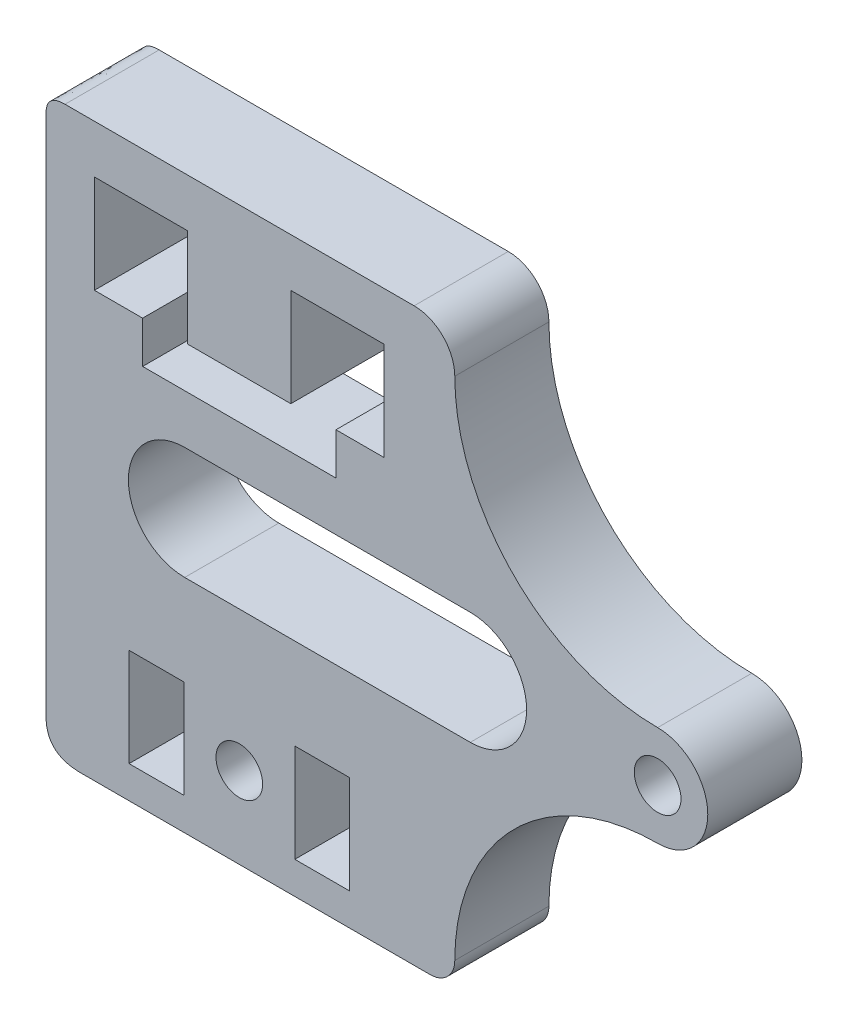
SolidWorks part; units mm, degrees
material "Acrylic (Medium-high impact)"
ref_plane "Front Plane" through (0, 0, 0) normal (0, 0, 1) x (1, 0, 0)
ref_plane "Top Plane" through (0, 0, 0) normal (0, 1, 0) x (1, 0, 0)
ref_plane "Right Plane" through (0, 0, 0) normal (1, 0, 0) x (0, 0, -1)
sketch "Sketch1" plane through (0, 0, 0) normal (0, 0, 1) x (1, 0, 0)
  line L0 (405.5669, 551.1889) -> (405.5669, 553.7889)
  line L1 (396.3551, 553.7889) -> (402.763, 553.7889)
  line L2 (393.5512, 553.7889) -> (393.5512, 551.1889)
  line L3 (393.5512, 551.1889) -> (405.5669, 551.1889)
  line L4 (390.5551, 559.8889) -> (390.5551, 553.7889)
  line L5 (393.5512, 553.7889) -> (390.5551, 553.7889)
  line L6 (396.3551, 559.8889) -> (390.5551, 559.8889)
  line L7 (396.3551, 553.7889) -> (396.3551, 559.8889)
  line L8 (405.5669, 553.7889) -> (408.563, 553.7889)
  line L9 (408.563, 553.7889) -> (408.563, 559.8889)
  line L10 (402.763, 559.8889) -> (402.763, 553.7889)
  line L11 (408.563, 559.8889) -> (402.763, 559.8889)
  line L12 (392.709, 535.4889) -> (392.709, 529.3889)
  line L13 (392.709, 529.3889) -> (396.109, 529.3889)
  line L14 (396.109, 535.4889) -> (392.709, 535.4889)
  line L15 (396.109, 529.3889) -> (396.109, 535.4889)
  line L16 (403.009, 529.3889) -> (406.4091, 529.3889)
  line L17 (406.4091, 529.3889) -> (406.4091, 535.4889)
  line L18 (403.009, 535.4889) -> (403.009, 529.3889)
  line L19 (406.4091, 535.4889) -> (403.009, 535.4889)
  line L20 (388.7281, 562.8889) -> (410.4246, 562.8889)
  line L21 (387.5551, 561.7172) -> (387.5551, 529.5596)
  line L22 (389.7281, 527.3889) -> (411.4246, 527.3889)
  line L23 (-605.591, 535.4889) -> (49394.409, 535.4889) construction
  line L24 (396.1657, 548.1389) -> (413.9157, 548.1389)
  line L25 (396.1657, 541.1389) -> (413.9157, 541.1389)
  line L26 (-600.441, 544.6389) -> (49399.559, 544.6389) construction
  line L27 (398.109, 532.4389) -> (396.109, 532.4389) construction
  line L28 (401.009, 532.4389) -> (403.009, 532.4389) construction
  line L29 (399.559, -466.6171) -> (399.559, 49533.3829) construction
  line L30 (425.559, -455.7473) -> (425.559, 49544.2527) construction
  line L31 (-608.8734, 553.7889) -> (49391.1266, 553.7889) construction
  line L32 (421.909, 544.6389) -> (421.909, 535.4889) construction
  line L33 (421.909, 544.6389) -> (421.909, 553.7889) construction
  line L34 (412.9514, 560.3621) -> (412.9514, 528.9157) construction
  circle A0 centre (425.559, 544.6389) radius 1.45
  arc A1 (396.1657, 548.1389) -> (396.1657, 541.1389) centre (396.1657, 544.6389) ccw
  circle A2 centre (399.559, 532.4389) radius 1.45
  arc A3 (412.9514, 528.9157) -> (425.559, 541.5233) centre (425.559, 528.9157) cw
  arc A4 (412.9514, 560.3621) -> (425.559, 547.7545) centre (425.559, 560.3621) ccw
  arc A5 (425.559, 547.7545) -> (425.559, 541.5233) centre (425.559, 544.6389) cw
  arc A7 (413.9157, 548.1389) -> (413.9157, 541.1389) centre (413.9157, 544.6389) cw
  arc A8 (411.4246, 527.3889) -> (412.9514, 528.9157) centre (411.4246, 528.9157) ccw
  arc A9 (410.4246, 562.8889) -> (412.9514, 560.3621) centre (410.4246, 560.3621) cw
  spline S36 degree 2 poles (387.5551, 561.7172) (387.4906, 562.8889) (388.7281, 562.8889) knots 0 0 0 1 1 1
  spline S37 degree 2 poles (387.5551, 529.5596) (387.4355, 527.3889) (389.7281, 527.3889) knots 0 0 0 1 1 1
  point P26 (399.559, 544.6389)
  point P30 (399.559, 553.7889)
  point P38 (394.409, 535.4889)
  point P40 (412.9514, 544.6389)
  dimension "D5" = 2.9
  dimension "D12" = 6.1
  dimension "D18" = 6.4078
  dimension "D2" = 3.4
  dimension "D3" = 5.8
  dimension "D4" = 2.6
  dimension "D6" = 2
  dimension "D7" = 18.3
  dimension "D8" = 2
  dimension "D9" = 3
  dimension "D10" = 3
  dimension "D11" = 26
  dimension "D13" = 12.0157
  dimension "D15" = 31.4465
  dimension "D17" = 17.75
  dimension "D19" = 13.3924
  dimension "D20" = 22.35
  dimension "D21" = 7
extrude "Boss-Extrude2" add sketch "Sketch1" along normal blind 5.85
